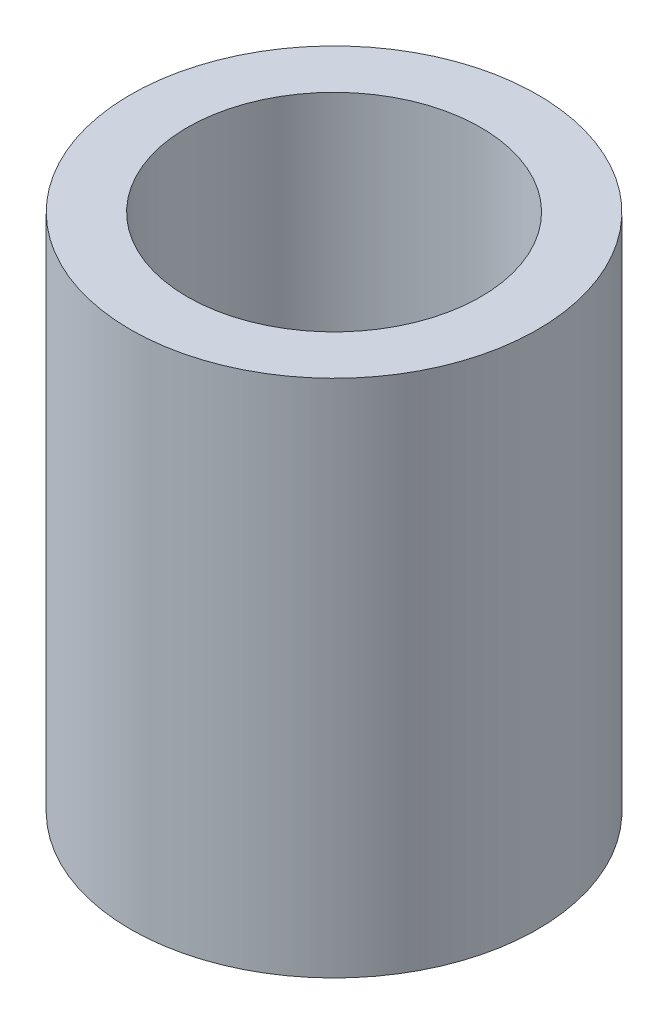
SolidWorks part; units mm, degrees
ref_plane "Front Plane" through (0, 0, 0) normal (0, 0, 1) x (1, 0, 0)
ref_plane "Top Plane" through (0, 0, 0) normal (0, 1, 0) x (1, 0, 0)
ref_plane "Right Plane" through (0, 0, 0) normal (1, 0, 0) x (0, 0, -1)
sketch "Sketch1" plane through (0, 0, 0) normal (0, 1, 0) x (1, 0, 0)
  circle A0 centre (0, 0) radius 20
  dimension "SLEEVE_OD" = 40
extrude "Boss-Extrude1" add sketch "Sketch1" along normal blind 51.0344
sketch "Sketch2" plane through (0, 0, 0) normal (0, 1, 0) x (1, 0, 0)
  circle A0 centre (0, 0) radius 14.4187
  dimension "BORE_D" = 28.8374
extrude "Cut-Extrude1" cut sketch "Sketch2" along normal through all
chamfer "Chamfer1" distance 3.1074 angle 60 rebuild error yes
